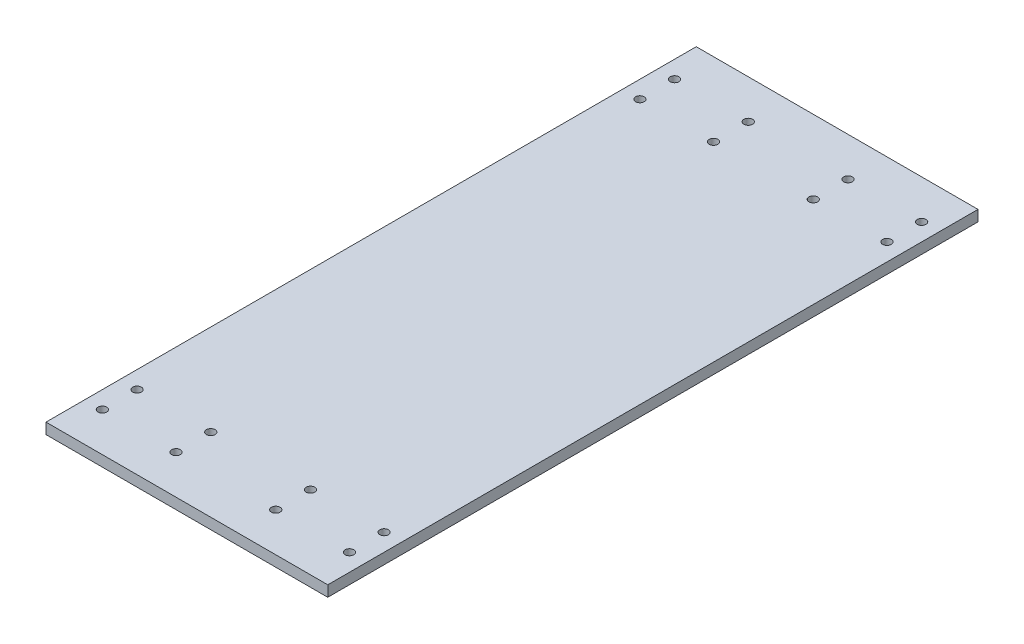
SolidWorks part; units mm, degrees
ref_plane "Front Plane" through (0, 0, 0) normal (0, 0, 1) x (1, 0, 0)
ref_plane "Top Plane" through (0, 0, 0) normal (0, 1, 0) x (1, 0, 0)
ref_plane "Right Plane" through (0, 0, 0) normal (1, 0, 0) x (0, 0, -1)
sketch "Sketch2" plane through (0, 0, 0) normal (0, 1, 0) x (1, 0, 0)
  line L1 (-65, -150) -> (65, -150)
  line L2 (-65, -150) -> (-65, 150)
  line L3 (-65, 150) -> (65, 150)
  line L4 (65, -150) -> (65, 150)
  line L5 (-65, -150) -> (65, 150) construction
  line L6 (-65, 150) -> (65, -150) construction
  point P0 (0, 0)
  dimension "D1" = 300
  dimension "D2" = 130
extrude "Boss-Extrude1" add sketch "Sketch2" along normal blind 5
sketch "Sketch3" plane through (0, 5, 0) normal (0, 1, 0) x (1, 0, 0)
  line L0 (-65, 150) -> (-65, -150) construction
  line L1 (65, 150) -> (-65, 150) construction
  circle A0 centre (-57, 132) radius 2
  circle A1 centre (-57, 116) radius 2
  circle A2 centre (-23, 132) radius 2
  circle A3 centre (-23, 116) radius 2
  dimension "D1" = 4
  dimension "D2" = 4
  dimension "D3" = 4
  dimension "D4" = 4
  dimension "D5" = 8
  dimension "D6" = 34
  dimension "D7" = 18
  dimension "D8" = 16
extrude "Cut-Extrude1" cut sketch "Sketch3" against normal blind 10
mirror "Mirror1" about plane through (0, 0, 0) normal (0, 0, 1) of "Cut-Extrude1" second plane through (0, 0, 0) second plane normal (1, 0, 0)
